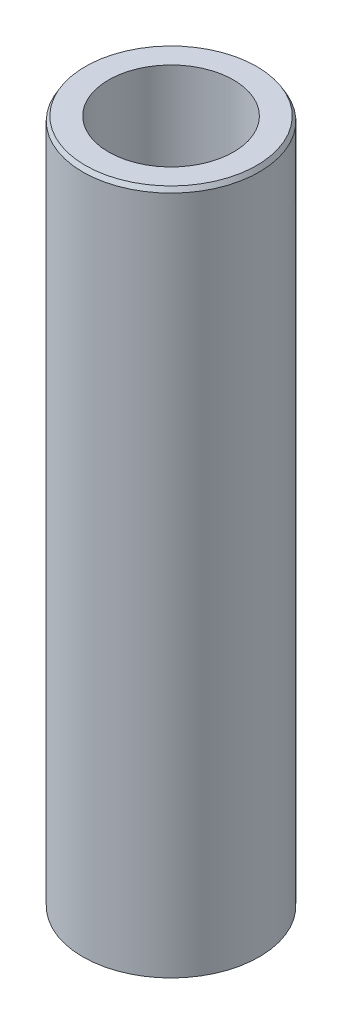
SolidWorks part; units mm, degrees
ref_plane "Front Plane" through (0, 0, 0) normal (0, 0, 1) x (1, 0, 0)
ref_plane "Top Plane" through (0, 0, 0) normal (0, 1, 0) x (1, 0, 0)
ref_plane "Right Plane" through (0, 0, 0) normal (1, 0, 0) x (0, 0, -1)
sketch "Sketch1" plane through (0, 0, 0) normal (0, 1, 0) x (1, 0, 0)
  circle A0 centre (0, 0) radius 25
  dimension "SHAFT_OD" = 50
extrude "Boss-Extrude1" add sketch "Sketch1" along normal blind 194.4784
sketch "Sketch2" plane through (0, 0, 0) normal (0, 1, 0) x (1, 0, 0)
  circle A0 centre (0, 0) radius 17.6989
  dimension "BORE_D" = 35.3978
extrude "Cut-Extrude1" cut sketch "Sketch2" along normal through all
chamfer "Chamfer1" distance 1.2487 angle 30 2 edges at (0, 194.4784, 25) (0, 0, 25) first distance on face at (0, 194.4784, 25) first distance on face at (0, 0, 17.6989)
